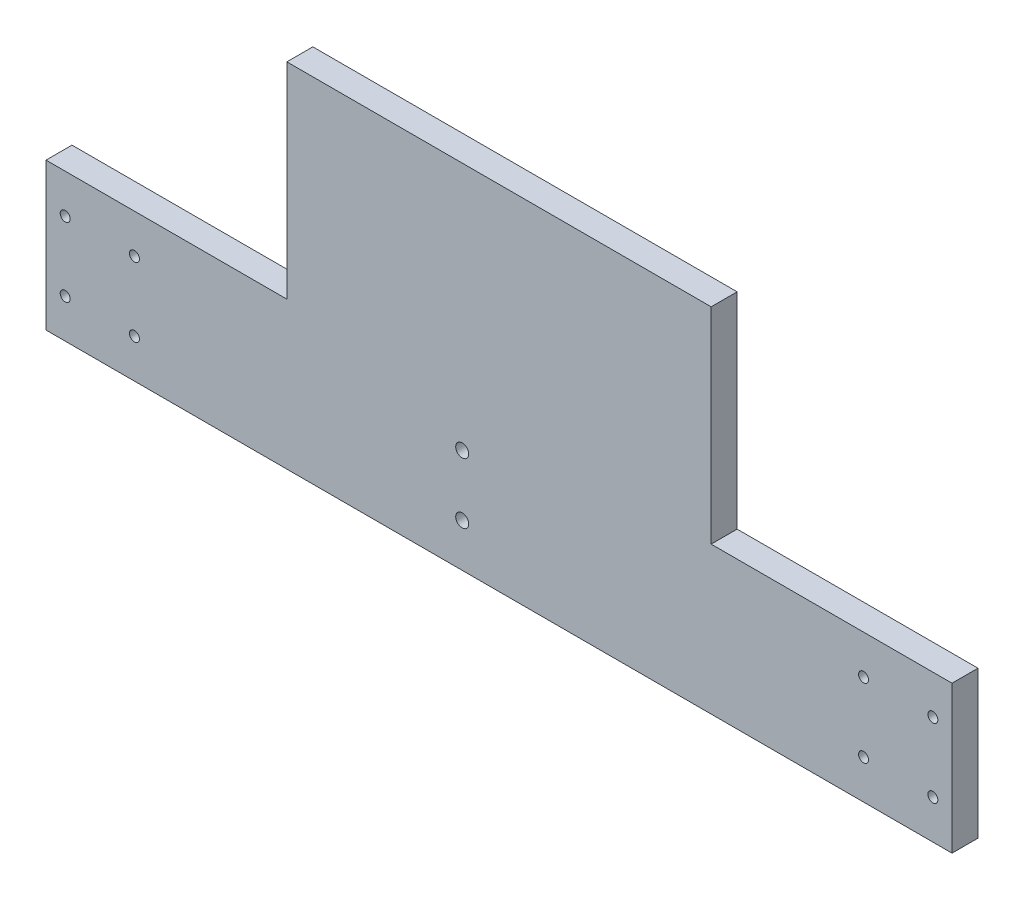
SolidWorks part; units mm, degrees
ref_plane "Plan de face" through (0, 0, 0) normal (0, 0, 1) x (1, 0, 0)
ref_plane "Plan de dessus" through (0, 0, 0) normal (0, 1, 0) x (1, 0, 0)
ref_plane "Plan de droite" through (0, 0, 0) normal (1, 0, 0) x (0, 0, -1)
sketch "Esquisse1" plane through (0, 0, 0) normal (0, 0, 1) x (1, 0, 0)
  line L0 (-104.63, 17) -> (-49, 17)
  line L1 (104.63, 17) -> (49, 17)
  line L2 (-104.63, 17) -> (-104.63, -17)
  line L3 (-104.63, -17) -> (104.63, -17)
  line L4 (104.63, 17) -> (104.63, -17)
  line L6 (-49, 17) -> (-49, 64.471)
  line L7 (-49, 64.471) -> (49, 64.471)
  line L8 (49, 17) -> (49, 64.471)
  dimension "D1" = 209.26
  dimension "D2" = 34
  dimension "D3" = 104.63
  dimension "D5" = 47.471
  dimension "D6" = 98
  dimension "D7" = 55.63
extrude "Boss.-Extru.1" add sketch "Esquisse1" along normal blind 6
sketch "Esquisse2" plane through (0, 0, 6) normal (0, 0, 1) x (1, 0, 0)
  line L0 (0, 49.0616) -> (0, -42.9956) construction
  line L1 (-104.63, 17) -> (-104.63, -17) construction
  line L3 (-104.63, -17) -> (104.63, -17) construction
  line L4 (-49, 17) -> (-104.63, 17) construction
  line L5 (-104.63, 17) -> (-104.63, -17) construction
  circle A0 centre (-100.2, 8) radius 1.15
  circle A1 centre (-84.2, 8) radius 1.15
  circle A2 centre (-84.2, -8) radius 1.15
  circle A3 centre (-100.2, -8) radius 1.15
  circle A4 centre (100.2, -8) radius 1.15
  circle A5 centre (84.2, -8) radius 1.15
  circle A6 centre (84.2, 8) radius 1.15
  circle A7 centre (100.2, 8) radius 1.15
  circle A8 centre (-8.5, 7) radius 1.5
  circle A9 centre (-8.5, -7) radius 1.5
  dimension "D1" = 2.3
  dimension "D2" = 2.3
  dimension "D3" = 2.3
  dimension "D4" = 2.3
  dimension "D12" = 3
  dimension "D14" = 3
  dimension "D5" = 4.43
  dimension "D6" = 9
  dimension "D7" = 9
  dimension "D8" = 16
  dimension "D9" = 16
  dimension "D10" = 16
  dimension "D11" = 16
  dimension "D13" = 10
  dimension "D15" = 10
  dimension "D16" = 14
  dimension "D17" = 8.5
  dimension "D18" = 4.43
extrude "Enlèv. mat.-Extru.1" cut sketch "Esquisse2" against normal blind 6
